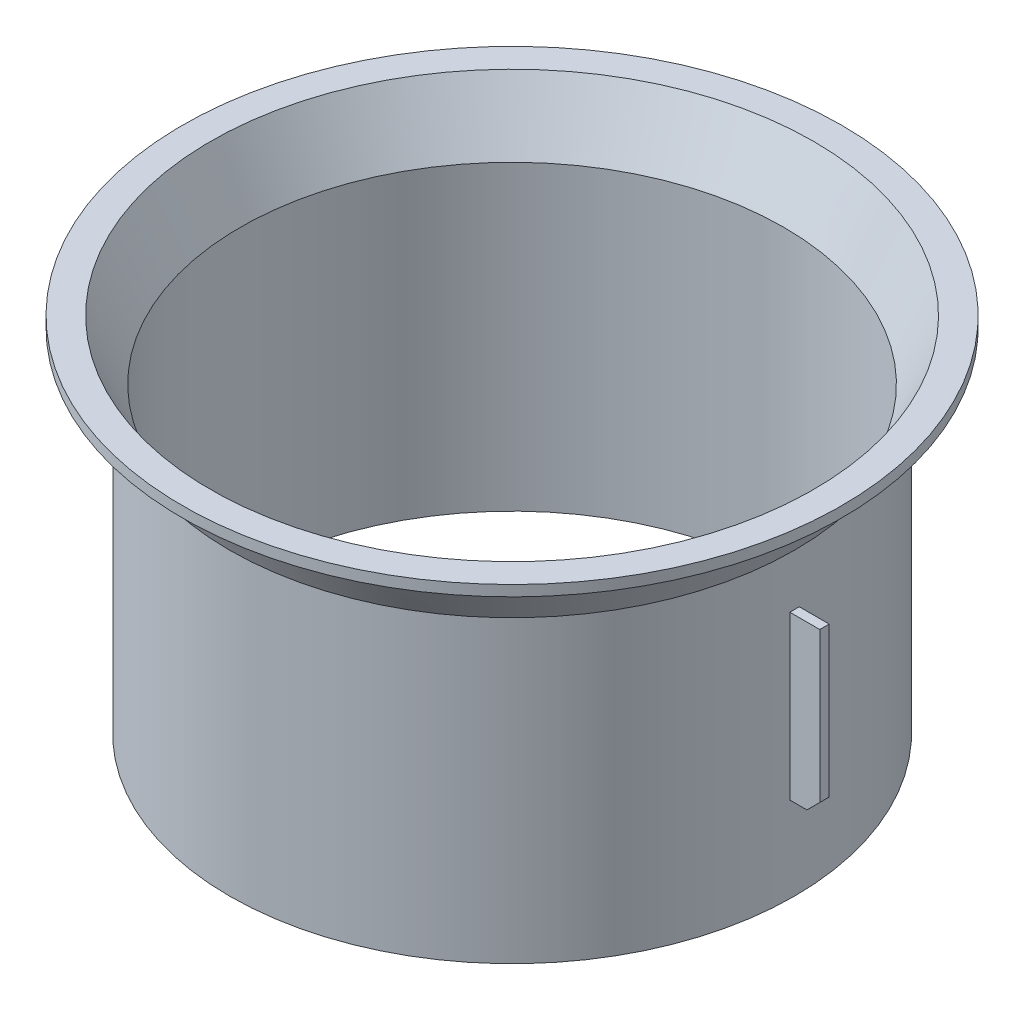
SolidWorks part; units mm, degrees
ref_plane "Front" through (0, 0, 0) normal (0, 0, 1) x (1, 0, 0)
ref_plane "Top" through (0, 0, 0) normal (0, 1, 0) x (1, 0, 0)
ref_plane "Right" through (0, 0, 0) normal (1, 0, 0) x (0, 0, -1)
sketch "Esquisse1" plane through (0, 0, 0) normal (0, 0, 1) x (1, 0, 0)
  line L0 (33, 0) -> (33, 35)
  line L1 (33, 35) -> (36, 41)
  line L2 (36, 41) -> (38.5, 41)
  line L3 (38.5, 41) -> (38.5, 42.25)
  line L4 (38.5, 42.25) -> (35.2275, 42.25)
  line L5 (35.2275, 42.25) -> (31.75, 35.2951)
  line L6 (31.75, 35.2951) -> (31.75, 0)
  line L7 (31.75, 0) -> (33, 0)
  line L8 (0, 0) -> (0, 46.75) construction
  point P11 (31.75, 32.6075)
  point P12 (31.75, 16.0038)
  dimension "D1" = 66
  dimension "D2" = 1.25
  dimension "D3" = 1.25
  dimension "D4" = 1.25
  dimension "D5" = 35
  dimension "D6" = 6
  dimension "D7" = 77
  dimension "D8" = 2.5
revolve "Révolution1" add sketch "Esquisse1" angle 360 about L8
sketch "Esquisse2" plane through (0, 0, 0) normal (0, -1, 0) x (1, 0, 0)
  line L0 (0, 0) -> (-33, 0) construction
  line L1 (-32.9954, 0.55) -> (-36.4954, 0.55)
  line L2 (-36.4954, -0.55) -> (-36.4954, 0.55)
  line L3 (-32.9954, 0.55) -> (-32.4954, 0)
  line L4 (-32.9954, -0.55) -> (-32.4954, 0)
  line L5 (0, 0) -> (0, 9.7933) construction
  line L6 (-32.9954, -0.55) -> (-36.4954, -0.55)
  line L7 (32.9954, -0.55) -> (36.4954, -0.55)
  line L8 (32.9954, -0.55) -> (32.4954, 0)
  line L9 (32.9954, 0.55) -> (32.4954, 0)
  line L10 (36.4954, -0.55) -> (36.4954, 0.55)
  line L11 (32.9954, 0.55) -> (36.4954, 0.55)
  circle A0 centre (0, 0) radius 33 construction
  dimension "D1" = 1.1
  dimension "D2" = 3.5
  dimension "D3" = 0.5
extrude "Boss.-Extru.1" add sketch "Esquisse2" against normal blind 19 from offset 10 offset against normal yes
chamfer "Chanfrein1" distance 1.5 angle 45 2 edges at (36.4954, 10, 0) (-36.4954, 10, 0)
